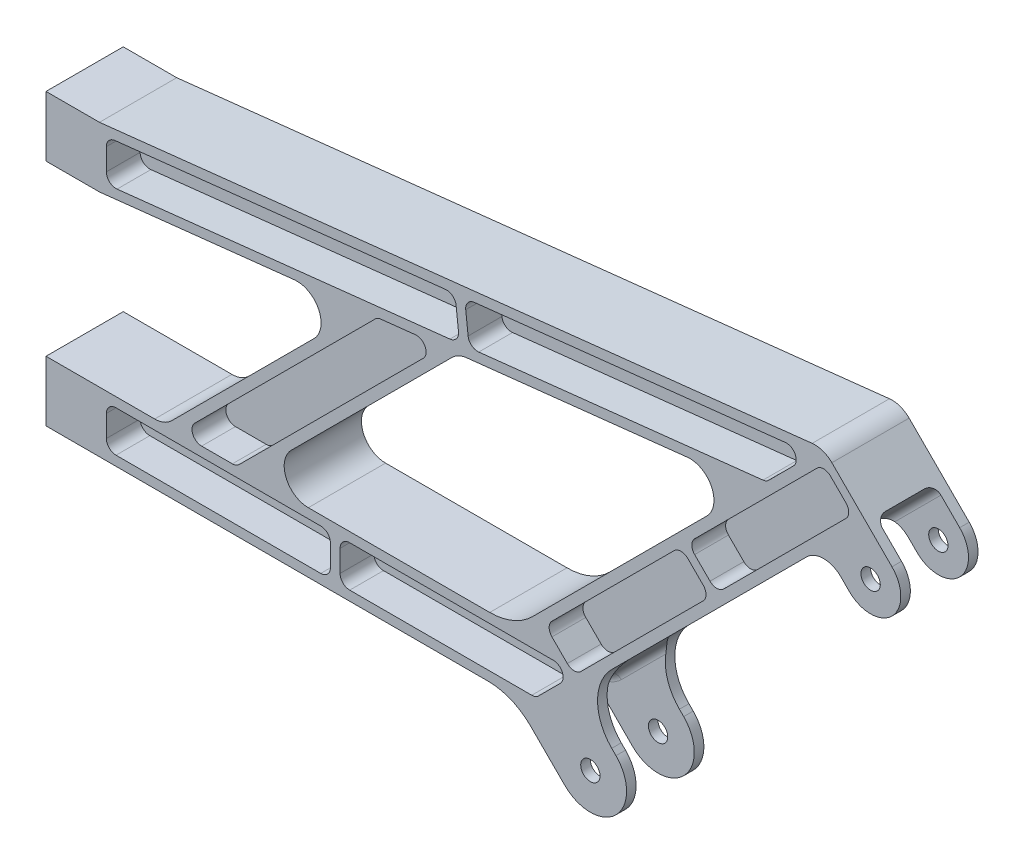
SolidWorks part; units mm, degrees
material "6061-T6 (SS)"
ref_plane "Front Plane" through (0, 0, 0) normal (0, 0, 1) x (1, 0, 0)
ref_plane "Top Plane" through (0, 0, 0) normal (0, 1, 0) x (1, 0, 0)
ref_plane "Right Plane" through (0, 0, 0) normal (1, 0, 0) x (0, 0, -1)
sketch "Sketch1" plane through (0, 0, 0) normal (0, 0, 1) x (1, 0, 0)
  line L1 (-157.7639, -90.8401) -> (-232.9187, -90.8401)
  line L2 (-67.8181, -11.2496) -> (-140.0863, -83.5177)
  line L3 (-16.0497, 33.7315) -> (8.8396, 8.8381)
  line L4 (-12.3744, -5.3033) -> (-8.8388, -8.8388)
  line L5 (-26.5165, -5.3033) -> (-107.2487, -86.0355)
  line L6 (-140.8326, -123.1624) -> (-126.6942, -137.3008)
  line L7 (-158.5102, -115.8401) -> (-341.5776, -115.8401)
  line L8 (-341.5776, -115.8401) -> (-341.5776, -90.8401)
  line L9 (-296.5583, -90.8401) -> (-341.5776, -90.8401)
  line L11 (-341.5776, -20.8403) -> (-319.4176, -20.8403)
  line L12 (-341.5776, -20.8403) -> (-341.5776, 4.1597)
  line L13 (-341.5776, 4.1597) -> (-319.4176, 4.1597)
  line L14 (-107.2487, -114.3198) -> (-105.481, -116.0876)
  line L15 (-319.4176, 4.1597) -> (-24.2138, 36.6012)
  line L17 (-289.4872, -87.9111) -> (-230.5597, -28.9836)
  line L18 (-75.9816, 5.7616) -> (-167.3954, -4.2843)
  line L19 (-239.9897, -73.769) -> (-173.3741, -7.1534)
  line L20 (-238.7231, -11.9724) -> (-319.4176, -20.8403)
  arc A4 (8.8388, -8.8388) -> (8.8396, 8.8381) centre (0, 0) ccw
  arc A5 (-8.8388, -8.8388) -> (8.8388, -8.8388) centre (0, 0) ccw
  arc A6 (-12.3744, -5.3033) -> (-26.5165, -5.3033) centre (-19.4454, -12.3744) ccw
  arc A7 (-107.2487, -86.0355) -> (-107.2487, -114.3198) centre (-93.1066, -100.1777) ccw
  arc A8 (-105.481, -137.3008) -> (-105.481, -116.0876) centre (-116.0876, -126.6942) ccw
  arc A9 (-126.6942, -137.3008) -> (-105.481, -137.3008) centre (-116.0876, -126.6942) ccw
  circle A12 centre (-116.0876, -126.6942) radius 4
  circle A13 centre (0, 0) radius 4
  arc A15 (-158.5102, -115.8401) -> (-140.8326, -123.1624) centre (-158.5102, -140.8401) cw
  arc A16 (-157.7639, -90.8401) -> (-140.0863, -83.5177) centre (-157.7639, -65.8401) ccw
  arc A20 (-67.8181, -11.2496) -> (-75.9816, 5.7616) centre (-74.8892, -4.1785) ccw
  arc A21 (-16.0497, 33.7315) -> (-24.2138, 36.6012) centre (-23.1214, 26.661) ccw
  arc A22 (-173.3741, -7.1534) -> (-167.3954, -4.2843) centre (-166.3031, -14.2245) cw
  arc A23 (-232.9187, -90.8401) -> (-239.9897, -73.769) centre (-232.9187, -80.8401) cw
  arc A25 (-296.5583, -90.8401) -> (-289.4872, -87.9111) centre (-296.5583, -80.8401) ccw
  arc A26 (-238.7231, -11.9724) -> (-230.5597, -28.9836) centre (-237.6307, -21.9125) cw
  point P26 (0, 0)
  point P38 (-319.0115, -20.8403)
  point P50 (0, 0)
  point P51 (0, 0)
  point P52 (-341.5776, -90.8401)
  point P54 (-341.5776, -115.8401)
  dimension "D2" = 25
  dimension "D3" = 25
  dimension "D7" = 10
  dimension "D9" = 22.16
  dimension "D6" = 25
  dimension "D1" = 25
  dimension "D4" = 25
  dimension "D5" = 25
  dimension "D8" = 119.9998
extrude "Boss-Extrude1" add sketch "Sketch1" along normal blind 32
sketch "Sketch2" plane through (0, 0, 32) normal (0, 0, 1) x (1, 0, 0)
  line L0 (-107.2487, -86.0355) -> (-26.5165, -5.3033) construction
  line L1 (-137.5386, -110.6685) -> (-128.5386, -101.6685)
  line L2 (-131.367, -94.8401) -> (-215.77, -94.8401)
  line L3 (-67.8181, -11.2496) -> (-140.0863, -83.5177) construction
  line L4 (-107.2487, -86.0355) -> (-26.5165, -5.3033)
  line L5 (-67.8181, -11.2496) -> (-140.0863, -83.5177)
  line L6 (-22.272, 28.6397) -> (-72.893, -21.9813)
  line L7 (-119.9767, -93.1066) -> (-69.3575, -42.4874)
  line L8 (-131.9975, -86.7426) -> (-125.6335, -93.1066)
  line L9 (-10.2515, 22.275) -> (-16.6149, 28.6394)
  line L10 (-64.9897, -14.078) -> (-137.2579, -86.3462) construction
  line L11 (-110.0772, -83.2071) -> (-29.3449, -2.4749) construction
  line L12 (-341.5776, -115.8401) -> (-158.5102, -115.8401) construction
  line L13 (-341.5776, -115.8401) -> (-158.5102, -115.8401)
  line L14 (-312.5776, -111.8401) -> (-227.77, -111.8401)
  line L15 (-341.5776, -111.8401) -> (-158.5102, -111.8401) construction
  line L16 (-341.5776, -90.8401) -> (-341.5776, -115.8401) construction
  line L17 (-316.5776, -98.8401) -> (-316.5776, -107.8401)
  line L18 (-157.7639, -90.8401) -> (-232.9187, -90.8401) construction
  line L19 (8.8396, 8.8381) -> (-16.0497, 33.7315) construction
  line L20 (-140.8326, -123.1624) -> (-126.6942, -137.3008) construction
  line L21 (-65.1149, -38.2448) -> (-77.1357, -26.224) construction
  line L22 (-72.893, -27.6382) -> (-66.5291, -34.0022)
  line L23 (-75.7215, -30.4666) -> (-69.3575, -36.8306)
  line L24 (-81.3783, -30.4666) -> (-131.9975, -81.0858)
  line L25 (-60.8722, -34.0022) -> (-10.2517, 16.6183)
  line L26 (-221.77, -94.8401) -> (-221.77, -111.8401) construction
  line L27 (-219.77, -98.8401) -> (-219.77, -107.8401)
  line L28 (-223.77, -98.8401) -> (-223.77, -107.8401)
  line L29 (-215.77, -111.8401) -> (-140.367, -111.8401)
  line L30 (-227.77, -94.8401) -> (-312.5776, -94.8401)
  line L36 (-319.5776, -20.8401) -> (-319.5776, 4.1599) construction
  line L38 (-313.0146, 0.8393) -> (-176.1091, 15.8845)
  line L39 (-24.2138, 36.6012) -> (-319.4176, 4.1597) construction
  line L40 (-312.1407, -16.167) -> (-174.2521, -1.0137)
  line L41 (-75.9816, 5.7616) -> (-167.3954, -4.2843) construction
  line L42 (-316.5776, -3.1368) -> (-316.5776, -12.191)
  line L43 (-32.0118, 24.5568) -> (-42.1838, 14.3847)
  line L44 (-170.145, 16.5399) -> (-168.288, -0.3583) construction
  line L45 (-171.6961, 12.3454) -> (-170.713, 3.3993)
  line L46 (-167.7201, 12.7824) -> (-166.7369, 3.8362)
  line L47 (-164.181, 17.1954) -> (-35.2771, 31.3613)
  line L48 (-162.3239, 0.2971) -> (-44.5753, 13.2371)
  line L49 (-205.2482, -9.329) -> (-279.9309, -84.0116)
  line L50 (-230.5597, -28.9836) -> (-289.4872, -87.9111) construction
  line L51 (-185.292, -13.4144) -> (-261.5461, -89.6685)
  line L52 (-173.3741, -7.1534) -> (-239.9897, -73.769) construction
  line L53 (-202.8567, -8.1813) -> (-188.5574, -6.6099)
  line L54 (-277.1024, -90.8401) -> (-264.3745, -90.8401)
  line L55 (-341.5776, 4.1597) -> (-341.5776, -20.8403) construction
  arc A0 (-22.272, 28.6397) -> (-16.6149, 28.6394) centre (-19.4436, 25.8113) cw
  arc A1 (-10.2517, 16.6183) -> (-10.2515, 22.275) centre (-13.0801, 19.4468) ccw
  arc A2 (-119.9767, -93.1066) -> (-125.6335, -93.1066) centre (-122.8051, -90.2782) cw
  arc A3 (-131.9975, -81.0858) -> (-131.9975, -86.7426) centre (-129.169, -83.9142) ccw
  arc A4 (-312.5776, -111.8401) -> (-316.5776, -107.8401) centre (-312.5776, -107.8401) cw
  arc A5 (-312.5776, -94.8401) -> (-316.5776, -98.8401) centre (-312.5776, -98.8401) ccw
  arc A6 (-140.367, -111.8401) -> (-137.5386, -110.6685) centre (-140.367, -107.8401) ccw
  arc A7 (-128.5386, -101.6685) -> (-131.367, -94.8401) centre (-131.367, -98.8401) ccw
  arc A8 (-75.7215, -30.4666) -> (-81.3783, -30.4666) centre (-78.5499, -33.295) ccw
  arc A9 (-69.3575, -36.8306) -> (-69.3575, -42.4874) centre (-72.1859, -39.659) cw
  arc A10 (-66.5291, -34.0022) -> (-60.8722, -34.0022) centre (-63.7006, -31.1737) ccw
  arc A11 (-72.893, -27.6382) -> (-72.893, -21.9813) centre (-70.0646, -24.8098) cw
  arc A12 (-223.77, -107.8401) -> (-227.77, -111.8401) centre (-227.77, -107.8401) cw
  arc A13 (-219.77, -107.8401) -> (-215.77, -111.8401) centre (-215.77, -107.8401) ccw
  arc A14 (-219.77, -98.8401) -> (-215.77, -94.8401) centre (-215.77, -98.8401) cw
  arc A15 (-223.77, -98.8401) -> (-227.77, -94.8401) centre (-227.77, -98.8401) ccw
  arc A20 (-44.5753, 13.2371) -> (-42.1838, 14.3847) centre (-45.0122, 17.2132) ccw
  arc A21 (-35.2771, 31.3613) -> (-32.0118, 24.5568) centre (-34.8402, 27.3852) cw
  arc A22 (-166.7369, 3.8362) -> (-162.3239, 0.2971) centre (-162.7609, 4.2732) ccw
  arc A23 (-167.7201, 12.7824) -> (-164.181, 17.1954) centre (-163.744, 13.2193) cw
  arc A24 (-170.713, 3.3993) -> (-174.2521, -1.0137) centre (-174.6891, 2.9623) cw
  arc A25 (-171.6961, 12.3454) -> (-176.1091, 15.8845) centre (-175.6722, 11.9085) ccw
  arc A26 (-312.1407, -16.167) -> (-316.5776, -12.191) centre (-312.5776, -12.191) cw
  arc A27 (-313.0146, 0.8393) -> (-316.5776, -3.1368) centre (-312.5776, -3.1368) ccw
  arc A28 (-185.292, -13.4144) -> (-188.5574, -6.6099) centre (-188.1204, -10.586) ccw
  arc A29 (-205.2482, -9.329) -> (-202.8567, -8.1813) centre (-202.4198, -12.1574) cw
  arc A30 (-261.5461, -89.6685) -> (-264.3745, -90.8401) centre (-264.3745, -86.8401) cw
  arc A31 (-277.1024, -90.8401) -> (-279.9309, -84.0116) centre (-277.1024, -86.8401) cw
  point P34 (-316.5776, -111.8401)
  point P53 (-78.5499, -27.6382)
  point P58 (-63.7006, -36.8306)
  point P69 (-223.77, -111.8401)
  point P72 (-219.77, -111.8401)
  point P75 (-219.77, -94.8401)
  point P78 (-223.77, -94.8401)
  point P117 (-166.3, -0.1398)
  point P120 (-168.157, 16.7584)
  point P123 (-170.276, -0.5768)
  point P126 (-172.1331, 16.3215)
  dimension "D2" = 4
  dimension "D6" = 4
  dimension "D11" = 4
  dimension "D13" = 4
  dimension "D16" = 4
  dimension "D22" = 4
  dimension "D19" = 4
  dimension "D4" = 25
  dimension "D5" = 4
  dimension "D7" = 4
  dimension "D8" = 4
  dimension "D9" = 32
  dimension "D10" = 2
  dimension "D12" = 2
  dimension "D14" = 4
  dimension "D15" = 4
  dimension "D17" = 4
  dimension "D18" = 4
  dimension "D20" = 4
  dimension "D21" = 2
  dimension "D23" = 4
  dimension "D24" = 3
  dimension "D1" = 4
  dimension "D3" = 4
extrude "Cut-Extrude1" cut sketch "Sketch2" against normal blind 14 contours L38 A27 L42 A26 L40 A24 L45 A25 | A23 L46 A22 L48 A20 L43 A21 L47 | A31 L54 A30 L51 A28 L53 A29 L49 | A11 L22 A10 L25 A1 L9 A0 L6 | A9 L23 A8 L24 A3 L8 A2 L7 | A14 L27 A13 L29 A6 L1 A7 L2 | L28 A15 L30 A5 L17 A4 L14 A12 region at (-175.3079, -103.1533, 32) region at (-41.5723, -2.6814, 32) region at (-100.6775, -61.7866, 32) region at (-270.1738, -103.3401, 32) region at (-243.8846, -0.128, 32) region at (-100.9045, 15.7508, 32) region at (-232.8243, -48.9709, 32)
ref_plane "Plane1" through (0, 0, 16) normal (0, 0, 1) x (1, 0, 0)
mirror "Mirror1" about plane through (0, 0, 16) normal (0, 0, 1) of "Cut-Extrude1"
sketch "Sketch3" plane through (0, 0, 16) normal (0, 0, 1) x (1, 0, 0)
  line L0 (-158.5102, -115.8401) -> (-141.1954, -115.8401)
  line L1 (-98.969, -77.7558) -> (-134.1243, -112.9111)
  line L2 (-107.2487, -86.0355) -> (-26.5165, -5.3033) construction
  line L3 (-158.5102, -115.8401) -> (-116.5971, -149.2186)
  line L4 (-116.5971, -149.2186) -> (-66.3597, -110.0186)
  line L5 (-66.3597, -110.0186) -> (-98.969, -77.7558)
  line L6 (-29.0156, -7.8024) -> (7.8698, 29.083)
  line L7 (7.8698, 29.083) -> (26.3533, -15.3879)
  line L8 (26.3533, -15.3879) -> (-12.041, -17.819)
  line L9 (-12.041, -17.819) -> (-29.0156, -7.8024)
  arc A0 (-134.1243, -112.9111) -> (-141.1954, -115.8401) centre (-141.1954, -105.8401) cw
  dimension "D1" = 10
extrude "Cut-Extrude2" cut sketch "Sketch3" against normal blind 12.0515 and the other way blind 12.0515
sketch "Sketch5" plane through (0, 0, 16) normal (0, 0, 1) x (1, 0, 0)
  line L0 (0, -24.7236) -> (0, -90.9031)
fillet "Fillet1" radius 4 2 edges at (-14.1417, 7.0715, 28.0515) (-14.1417, 7.0715, 3.9485)
fillet "Fillet2" radius 4 6 edges at (-149.8528, -115.8401, 3.9485) (-137.3686, -115.0789, 3.9485) (-149.8528, -115.8401, 28.0515) (-137.3686, -115.0789, 28.0515) (-120.6865, -99.4733, 3.9485) (-120.6865, -99.4733, 28.0515)
sketch "Sketch6" plane through (-341.5776, 0, 0) normal (-1, 0, 0) x (0, 0, 1)
  line L4 (0, -90.8401) -> (0, -115.8401)
  line L5 (0, -115.8401) -> (32, -115.8401)
  line L6 (32, -115.8401) -> (32, -90.8401)
  line L7 (32, -90.8401) -> (0, -90.8401)
  line L8 (0, -90.8401) -> (0, -115.8401)
  line L9 (0, -115.8401) -> (32, -115.8401)
  line L10 (32, -115.8401) -> (32, -90.8401)
  line L11 (32, -90.8401) -> (0, -90.8401)
  dimension "D1" = 0
sketch "Sketch7" plane through (-341.5776, 0, 0) normal (-1, 0, 0) x (0, 0, 1)
  line L0 (32, -115.8401) -> (32, -90.8401) construction
  line L1 (32, -90.8401) -> (0, -90.8401) construction
  line L2 (0, -90.8401) -> (0, -115.8401) construction
  line L3 (0, -115.8401) -> (32, -115.8401) construction
  line L4 (0, 4.1597) -> (0, -20.8403) construction
  line L5 (0, -20.8403) -> (32, -20.8403) construction
  line L6 (32, -20.8403) -> (32, 4.1597) construction
  line L7 (32, 4.1597) -> (0, 4.1597) construction
  line L8 (32, -115.8401) -> (32, -90.8401)
  line L9 (32, -90.8401) -> (0, -90.8401)
  line L10 (0, -90.8401) -> (0, -115.8401)
  line L11 (0, -115.8401) -> (32, -115.8401)
  line L12 (0, 4.1597) -> (0, -20.8403)
  line L13 (0, -20.8403) -> (32, -20.8403)
  line L14 (32, -20.8403) -> (32, 4.1597)
  line L15 (32, 4.1597) -> (0, 4.1597)
  line L16 (0, -115.8401) -> (32, -90.8401)
  line L17 (32, 4.1597) -> (0, -20.8403)
  line L18 (8, 4.1597) -> (8, -3.8403)
  line L19 (8, -3.8403) -> (0, -3.8403)
  line L20 (32, -12.8403) -> (24, -12.8403)
  line L21 (24, -12.8403) -> (24, -20.8403)
  line L22 (0, -98.8401) -> (8, -98.8401)
  line L23 (8, -98.8401) -> (8, -90.8401)
  line L24 (32, -107.8401) -> (24, -107.8401)
  line L25 (24, -107.8401) -> (24, -115.8401)
  circle A2 centre (24, -12.8403) radius 4
  circle A3 centre (8, -3.8403) radius 4
  circle A4 centre (8, -98.8401) radius 4
  circle A5 centre (24, -107.8401) radius 4
  dimension "D1" = 8
  dimension "D3" = 8
extrude "Cut-Extrude3" cut sketch "Sketch7" against normal blind 14 contours L19 A3 L18 | L18 A3 L19 | L20 A2 L21 | L21 A2 L20 | L24 A5 L25 | L25 A5 L24 | L22 A4 L23 | L23 A4 L22 region at (-341.5776, -109.5377, 25.6977) region at (-341.5776, -107.2742, 23.4341) region at (-341.5776, -99.406, 8.5659) region at (-341.5776, -97.1424, 6.3023) region at (-341.5776, -2.1426, 6.3023) region at (-341.5776, -4.4062, 8.5659) region at (-341.5776, -12.2744, 23.4341) region at (-341.5776, -14.5379, 25.6977)
